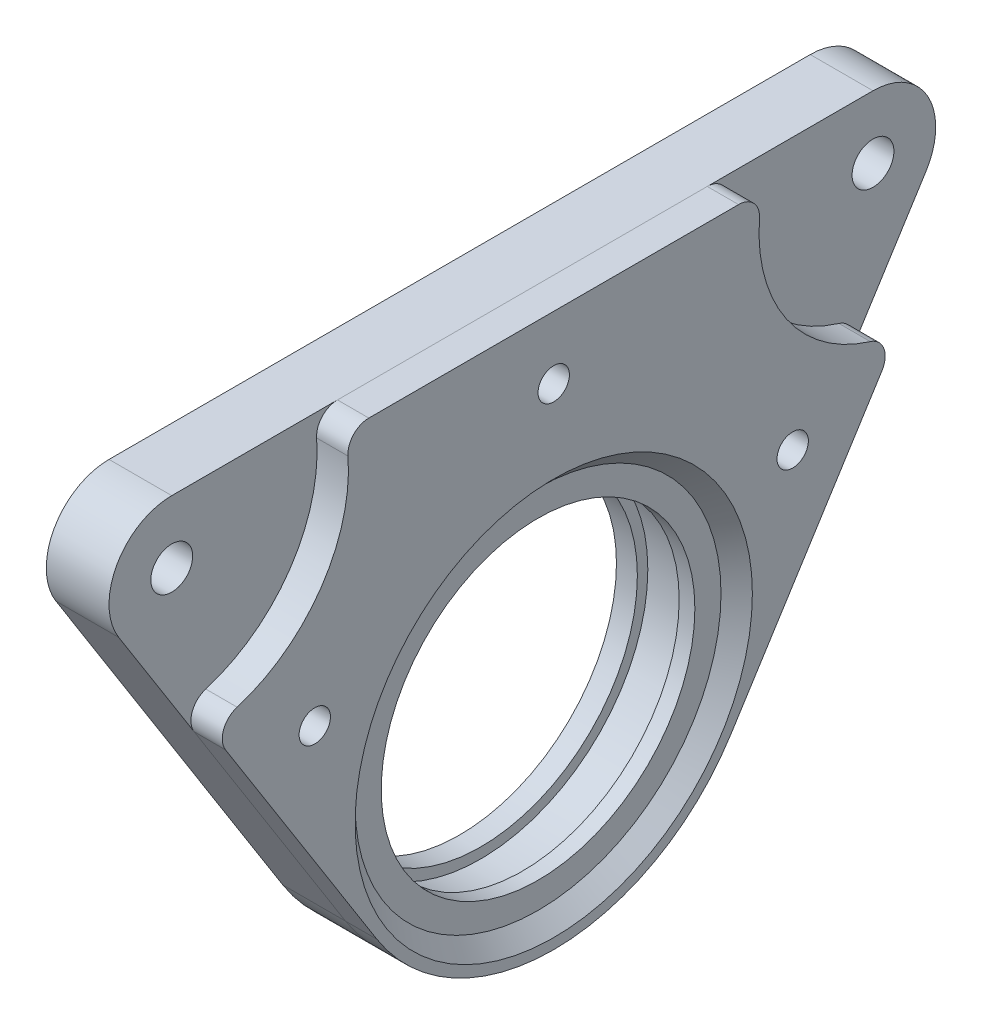
SolidWorks part; units mm, degrees
ref_plane "Front Plane" through (0, 0, 0) normal (0, 0, 1) x (1, 0, 0)
ref_plane "Top Plane" through (0, 0, 0) normal (0, 1, 0) x (1, 0, 0)
ref_plane "Right Plane" through (0, 0, 0) normal (1, 0, 0) x (0, 0, -1)
sketch "Sketch1" plane through (0, 0, 0) normal (1, 0, 0) x (0, 0, -1)
  circle A0 centre (0, 0) radius 15
  circle A1 centre (0, 0) radius 20
  dimension "D1" = 30
  dimension "D2" = 40
extrude "Boss-Extrude1" add sketch "Sketch1" along normal blind 2
sketch "Sketch2" plane through (2, 0, 0) normal (1, 0, 0) x (0, 0, -1)
  circle A0 centre (0, 0) radius 16
  circle A1 centre (0, 0) radius 20 construction
  circle A2 centre (0, 0) radius 20
  dimension "D1" = 32
extrude "Boss-Extrude2" add sketch "Sketch2" along normal blind 4
sketch "Sketch3" plane through (6, 0, 0) normal (1, 0, 0) x (0, 0, -1)
  line L0 (-33.5359, 26.8817) -> (0, 0) construction
  line L1 (0, 0) -> (33.5359, 26.8817) construction
  line L2 (-38.6088, 23.6778) -> (-16.9099, -10.6797)
  line L3 (-33.5359, 32.8817) -> (33.5359, 32.8817)
  line L4 (16.9099, -10.6797) -> (38.6088, 23.6778)
  circle A0 centre (-33.5359, 26.8817) radius 2
  circle A1 centre (33.5359, 26.8817) radius 2
  arc A2 (-33.5359, 32.8817) -> (-38.6088, 23.6778) centre (-33.5359, 26.8817) ccw
  arc A3 (38.6088, 23.6778) -> (33.5359, 32.8817) centre (33.5359, 26.8817) ccw
  circle A4 centre (0, 0) radius 20 construction
  arc A5 (16.9099, -10.6797) -> (-16.9099, -10.6797) centre (0, 0) ccw
  circle A6 centre (-33.5359, 26.8817) radius 6 construction
  circle A7 centre (33.5359, 26.8817) radius 6 construction
  dimension "D1" = 4
  dimension "D2" = 102.57
  dimension "D3" = 42.98
  dimension "D4" = 4
extrude "Boss-Extrude3" add sketch "Sketch3" against normal up to surface (6 mm away) up to face at (0, 0, -20)
sketch "Sketch4" plane through (6, 0, 0) normal (1, 0, 0) x (0, 0, -1)
  line L0 (-33.5359, 26.8817) -> (-22.8562, 9.9718) construction
  line L1 (-38.6088, 23.6778) -> (-16.9099, -10.6797) construction
  line L2 (0, 0) -> (0, 15) construction
  line L3 (33.5359, 26.8817) -> (22.8562, 9.9718) construction
  circle A0 centre (-22.8562, 9.9718) radius 2.4
  circle A2 centre (0, 0) radius 15 construction
  circle A3 centre (22.8562, 9.9718) radius 2.4
  circle A4 centre (0, 26.8817) radius 2.4
  dimension "D1" = 4.8
  dimension "D2" = 20
extrude "Cut-Extrude1" cut sketch "Sketch4" against normal up to surface (6 mm away) up to face at (0, 14.2393, 0)
sketch "Sketch5" plane through (6, 0, 0) normal (1, 0, 0) x (0, 0, -1)
  line L0 (16.9099, -10.6797) -> (38.6088, 23.6778) construction
  line L3 (16.9099, -10.6797) -> (38.6088, 23.6778)
  line L4 (33.5359, 32.8817) -> (-33.5359, 32.8817)
  line L5 (-38.6088, 23.6778) -> (-16.9099, -10.6797)
  line L6 (16.9099, -10.6797) -> (32.9294, 14.6852)
  line L7 (20, 32.8817) -> (-20, 32.8817)
  line L8 (-32.9294, 14.6852) -> (-16.9099, -10.6797)
  circle A0 centre (0, 0) radius 15
  arc A1 (-32.9294, 14.6852) -> (-20, 32.8817) centre (-34.6339, 29.588) ccw
  circle A6 centre (0, 26.8817) radius 2.4
  circle A7 centre (0, 26.8817) radius 2.4 construction
  circle A8 centre (22.8562, 9.9718) radius 2.4
  circle A9 centre (22.8562, 9.9718) radius 2.4 construction
  circle A10 centre (-22.8562, 9.9718) radius 2.4
  circle A11 centre (-22.8562, 9.9718) radius 2.4 construction
  arc A12 (20, 32.8817) -> (32.9294, 14.6852) centre (34.6339, 29.588) ccw
  circle A14 centre (-22.8562, 9.9718) radius 1.5
  arc A15 (-16.9099, -10.6797) -> (16.9099, -10.6797) centre (0, 0) ccw
  arc A16 (38.6088, 23.6778) -> (33.5359, 32.8817) centre (33.5359, 26.8817) ccw
  arc A17 (-33.5359, 32.8817) -> (-38.6088, 23.6778) centre (-33.5359, 26.8817) ccw
  arc A18 (-16.9099, -10.6797) -> (16.9099, -10.6797) centre (0, 0) ccw
  circle A21 centre (0, 26.8817) radius 1.5
  circle A22 centre (22.8562, 9.9718) radius 1.5
  point P10 (0, 32.8817)
  dimension "D1" = 30
  dimension "D8" = 30
  dimension "D9" = 3
  dimension "D2" = 40
  dimension "D3" = 30
  dimension "D4" = 0
  dimension "D5" = 0
  dimension "D6" = 0
  dimension "D7" = 0
extrude "Boss-Extrude4" add sketch "Sketch5" along normal blind 3 separate body
fillet "Fillet1" radius 2 4 edges at (7.5, 14.6852, -32.9294) (7.5, 14.6852, 32.9294) (7.5, 32.8817, -20) (7.5, 32.8817, 20)
sketch "Sketch6" plane through (9, 0, 0) normal (1, 0, 0) x (0, 0, -1)
  circle A0 centre (0, 0) radius 17.5
  circle A1 centre (0, 0) radius 15 construction
  circle A2 centre (0, 0) radius 15
  dimension "D1" = 35
extrude "Cut-Extrude2" cut sketch "Sketch6" against normal blind 1.5
chamfer "Chamfer1" distance 1.5 angle 45 1 edges at (9, 0, -17.5)
